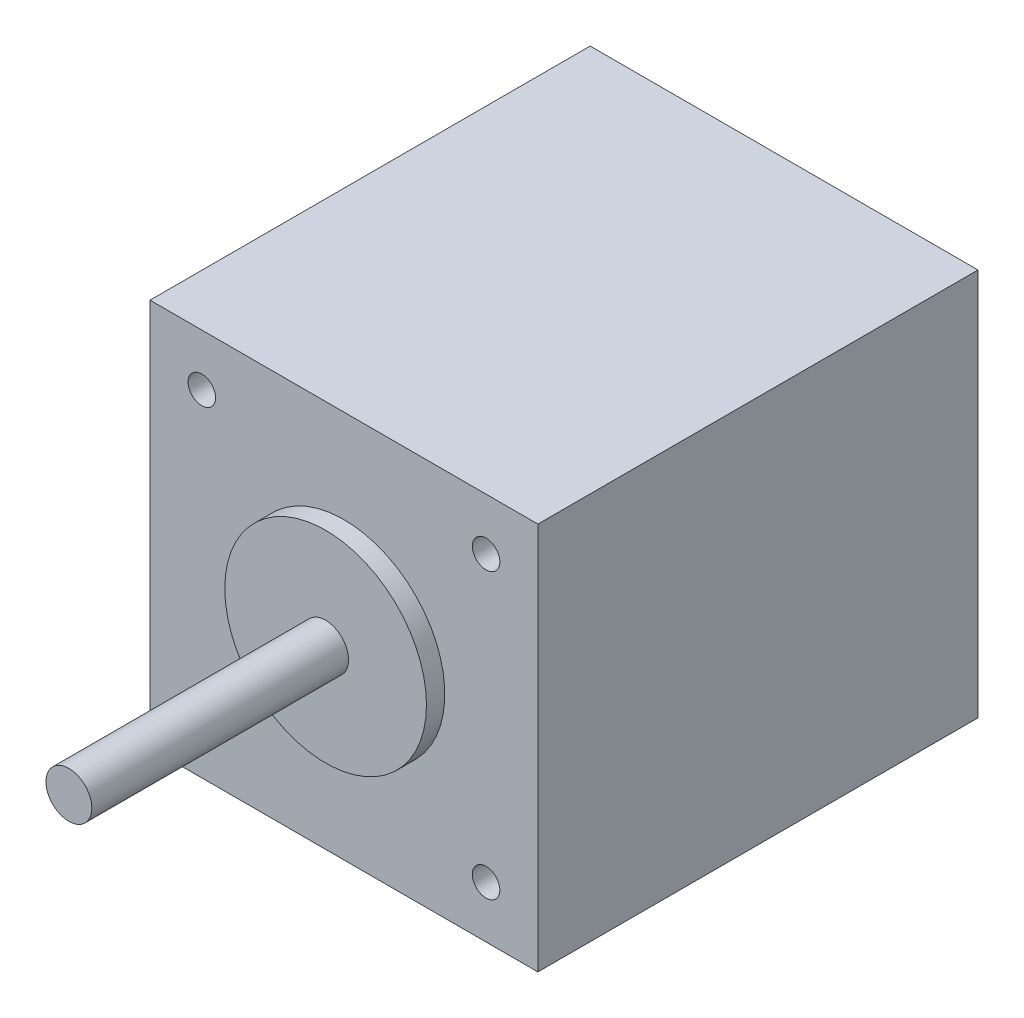
SolidWorks part; units mm, degrees
ref_plane "Спереди" through (0, 0, 0) normal (0, 0, 1) x (1, 0, 0)
ref_plane "Сверху" through (0, 0, 0) normal (0, 1, 0) x (1, 0, 0)
ref_plane "Справа" through (0, 0, 0) normal (1, 0, 0) x (0, 0, -1)
other "Configuration Table"
sketch "Эскиз1" plane through (0, 0, 0) normal (0, 0, 1) x (1, 0, 0)
  line L1 (-21.15, -21.15) -> (21.15, -21.15)
  line L2 (-21.15, -21.15) -> (-21.15, 21.15)
  line L3 (-21.15, 21.15) -> (21.15, 21.15)
  line L4 (21.15, -21.15) -> (21.15, 21.15)
  line L5 (-21.15, -21.15) -> (21.15, 21.15) construction
  line L6 (-21.15, 21.15) -> (21.15, -21.15) construction
  point P0 (0, 0)
  dimension "D1" = 42.3
  dimension "D2" = 42.3
extrude "Корпус" add sketch "Эскиз1" along normal blind 48
sketch "Эскиз2" plane through (0, 0, 0) normal (0, 0, 1) x (1, 0, 0)
  circle A0 centre (0, 0) radius 2.5
extrude "Вал_ПРЕДВ" add sketch "Эскиз2" along normal blind 78
sketch "Эскиз3" plane through (0, 0, 0) normal (0, 0, 1) x (1, 0, 0)
  circle A0 centre (0, 0) radius 11
  dimension "D1" = 22
extrude "Буртик_ПРЕДВ" add sketch "Эскиз3" along normal blind 50
sketch "Эскиз4" plane through (0, 0, 0) normal (0, 0, 1) x (1, 0, 0)
  circle A0 centre (0, 0) radius 8
  dimension "D1" = 16
sketch "Эскиз5" plane through (0, 0, 0) normal (0, 0, 1) x (1, 0, 0)
  circle A0 centre (-15.5, -15.5) radius 1.5
  circle A1 centre (-15.5, 15.5) radius 1.5
  circle A2 centre (15.5, -15.5) radius 1.5
  circle A3 centre (15.5, 15.5) radius 1.5
  dimension "D2" = 3
  dimension "D3" = 3
  dimension "D4" = 3
extrude "Крепеж_М3_ПРЕДВ" cut sketch "Эскиз5" against normal blind 4.5 from offset 48
equation "\"Мотор X ширина корпуса\"= 42.3"
equation "\"Мотор X высота корпуса\"= 42.3"
equation "\"Мотор X длина корпуса\"= 40"
equation "\"Мотор X вылет вала\"= 19.8"
equation "\"Мотор Y ширина корпуса\"= 42.3"
equation "\"Мотор Y высота корпуса\"= 42.3"
equation "\"Мотор Y длина корпуса\"= 48"
equation "\"Мотор Y вылет вала\"= 30"
equation "\"Мотор Z ширина корпуса\"= 42"
equation "\"Мотор Z высота корпуса\"= 42"
equation "\"Мотор Z длина корпуса\"= 40"
equation "\"Мотор Z вылет вала\"= 23"
equation "\"Мотор диаметр вала ПРЕДВ\"= 5"
equation "\"Мотор шаг крепления ПРЕДВ\"= 31"
equation "\"Мотор диаметр отверстий ПРЕДВ\"= 3"
equation "\"Мотор глубина отверстий ПРЕДВ\"= 4.5"
equation "\"Мотор диаметр буртика ПРЕДВ\"= 22"
equation "\"Мотор высота буртика ПРЕДВ\"= 2"
equation "\"Мотор диаметр шкива ПРЕДВ\"= 16"
equation "\"Мотор длина шкива ПРЕДВ\"= 12"
equation "\"Мотор отступ шкива ПРЕДВ\"= 5"
equation "\"Мотор X шаг градусов\"= 1.8"
equation "\"Мотор Y шаг градусов\"= 1.8"
equation "\"Мотор Z шаг градусов\"= 1.8"
equation "\"Мотор Y диаметр ротора\"= 25.78"
equation "\"D1@Эскиз1\" = \"Мотор Y ширина корпуса\""
equation "\"D1@Корпус\" = \"Мотор Y длина корпуса\""
equation "\"D1@Эскиз2\" = \"Мотор диаметр вала ПРЕДВ\""
equation "\"D1@Вал_ПРЕДВ\" = \"Мотор Y длина корпуса\" + \"Мотор Y вылет вала\""
equation "\"D1@Эскиз3\" = \"Мотор диаметр буртика ПРЕДВ\""
equation "\"D1@Буртик_ПРЕДВ\" = \"Мотор Y длина корпуса\" + \"Мотор высота буртика ПРЕДВ\""
equation "\"D1@Эскиз4\" = \"Мотор диаметр шкива ПРЕДВ\""
equation "\"D1@Эскиз5\" = \"Мотор диаметр отверстий ПРЕДВ\""
equation "\"D2@Эскиз5\" = \"Мотор диаметр отверстий ПРЕДВ\""
equation "\"D3@Эскиз5\" = \"Мотор диаметр отверстий ПРЕДВ\""
equation "\"D4@Эскиз5\" = \"Мотор диаметр отверстий ПРЕДВ\""
equation "\"D1@Крепеж_М3_ПРЕДВ\" = \"Мотор глубина отверстий ПРЕДВ\""
equation "\"D19@Крепеж_М3_ПРЕДВ\" = \"Мотор Y длина корпуса\""
equation "\"Ширина груза\"= 420"
equation "\"Глубина груза\"= 490"
equation "\"Высота груза\"= 297"
equation "\"Ширина ячейки\"= \"Ширина груза\" + 10"
equation "\"Глубина ячейки\"= \"Глубина груза\" + 10"
equation "\"Высота ячейки\"= \"Высота груза\" + 10 + 13"
equation "\"Колво ячеек ширина\"= 2"
equation "\"Колво ячеек высота\"= 2"
equation "\"Толщина стенки\" = 6"
equation "\"Крепление дверцы\"= 5 "
equation "\"Ширина рейки\"= \"Толщина шестерни\""
equation "\"Высота рейки\"= 20"
equation "\"Высота пола\"= \"Толщина стенки\" * 2"
equation "\"Колво полозьев\"= 5"
equation "\"Отступ рейки\"= 20"
equation "\"Глубина каретки\"= \"Глубина ячейки\" + 30 + \"Мотор Y высота корпуса\" + 20"
equation "\"Отступ шпильки\"= 26"
equation "\"Диаметр шпильки\"= 5"
equation "\"Длинна шпильки\"= ( \"Высота ячейки\" + \"Толщина стенки\" + \"Высота пола\" ) * \"Колво ячеек высота\" + ( \"Толщина стенки\" + \"Отступ рейки\" ) * 2 "
equation "\"Ширина пластины\"= 50  "
equation "\"Высота зона выгрузки\"= \"Высота ячейки\" * 2 + \"Толщина стенки\" * 2"
equation "\"Колво выгрузки\"= 1"
equation "\"Отступ крепления мотора фиксации\" = (\"Ширина пластины\" + 20 - \"Толщина стенки\") / 2"
equation "\"Ширина ячейки выгрузки\"= \"Ширина ячейки\" + \"Толщина стенки\" + \"Отступ крепления мотора фиксации\"*2"
equation "\"Длинна рейки\" = (\"Ширина ячейки\" + \"Толщина стенки\" + \"Крепление дверцы\") * \"Колво ячеек ширина\" + \"Ширина ячейки выгрузки\" * \"Колво выгрузки\" + \"Толщина стенки\" + \"Отступ крепления мотора фиксации\" * 2 - \"Крепление дверцы\" * \"Колво ячеек ширина\""
equation "\"Толщина шестерни\"= 10"
